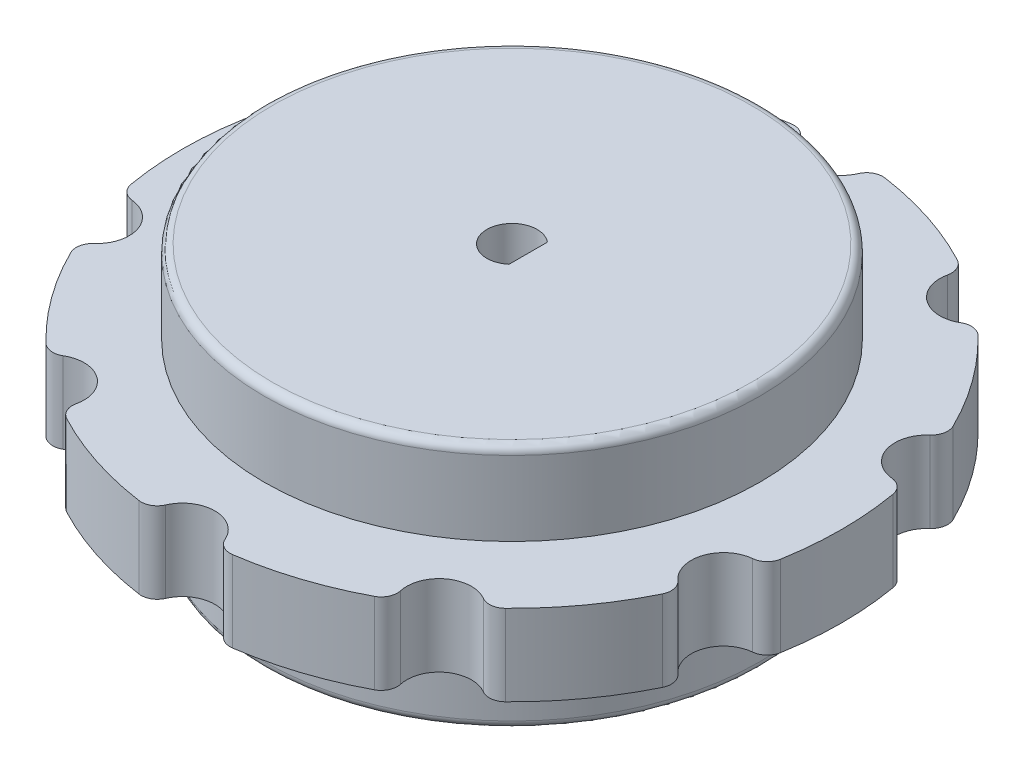
SolidWorks part; units mm, degrees
ref_plane "前视基准面" through (0, 0, 0) normal (0, 0, 1) x (1, 0, 0)
ref_plane "上视基准面" through (0, 0, 0) normal (0, 1, 0) x (1, 0, 0)
ref_plane "右视基准面" through (0, 0, 0) normal (1, 0, 0) x (0, 0, -1)
other "Configuration Table"
sketch "草图1" plane through (0, 0, 0) normal (0, 1, 0) x (1, 0, 0)
  circle A0 centre (0, 0) radius 15.3
  circle A1 centre (0, 0) radius 20.35
  circle A2 centre (0, 0) radius 13.7
  circle A3 centre (0, 20.35) radius 2
  dimension "D1" = 30.6
  dimension "D2" = 40.7
  dimension "D3" = 1.6
  dimension "D4" = 4
extrude "凸台-拉伸1" add sketch "草图1" along normal mid plane 15.2 contours A0 | A2
extrude "凸台-拉伸2" add sketch "草图1<3>" along normal mid plane 5 contours A1
sketch "草图1<3>" plane through (0, 0, 0) normal (0, 1, 0) x (1, 0, 0) same geometry as "草图1"
extrude "切除-拉伸1" cut sketch "草图1<4>" against normal through all both and the other way through all contours A3
sketch "草图1<4>" plane through (0, 0, 0) normal (0, 1, 0) x (1, 0, 0) same geometry as "草图1"
fillet "圆角1" radius 1 2 edges at (1.9976, 0, -20.2517) (-1.9976, 0, -20.2517)
pattern_circular "阵列(圆周)1" count 10 over 360 about axis through (0, 2.5, 0) along (0, -1, 0) of "切除-拉伸1", "圆角1"
fillet "圆角2" radius 0.5 2 edges at (0, -7.6, 15.3) (0, 7.6, 15.3)
extrude "凸台-拉伸3" add sketch "草图1<5>" along normal mid plane 7.8 contours A2
sketch "草图1<5>" plane through (0, 0, 0) normal (0, 1, 0) x (1, 0, 0) same geometry as "草图1"
extrude "凸台-拉伸5" add sketch "草图1<6>" along normal up to surface (7.6 mm away) from surface contours A2 up to face at (0, 7.6, 14.8) starting at face at (0, -7.6, 14.8)
sketch "草图1<6>" plane through (0, 0, 0) normal (0, 1, 0) x (1, 0, 0) same geometry as "草图1"
sketch "草图2" plane through (0, 2.5, 0) normal (0, 1, 0) x (1, 0, 0)
  line L0 (0, 20.35) -> (11.9614, 16.4635)
  line L1 (-11.9614, 16.4635) -> (0, 20.35)
  arc A0 (-1.834, 19.5523) -> (1.834, 19.5523) centre (0, 20.35) ccw construction
  arc A1 (10.0088, 16.8962) -> (12.9763, 14.7401) centre (11.9614, 16.4635) ccw construction
  arc A2 (-12.9763, 14.7401) -> (-10.0088, 16.8962) centre (-11.9614, 16.4635) ccw construction
  dimension "D1" = 12.577
  dimension "D2" = 12.577
sketch "草图4" plane through (0, -7.6, 0) normal (0, -1, 0) x (1, 0, 0)
  line L0 (1, 1.1843) -> (1, -1.1843)
  circle A0 centre (0, 0) radius 1.55
  circle A1 centre (0, 0) radius 3.1
  dimension "D1" = 3.1
  dimension "D2" = 6.2
  dimension "D3" = 1
extrude "切除-拉伸3" cut sketch "草图4" against normal through all contours L0 A0 region at (-0.1667, -7.6, 0)
